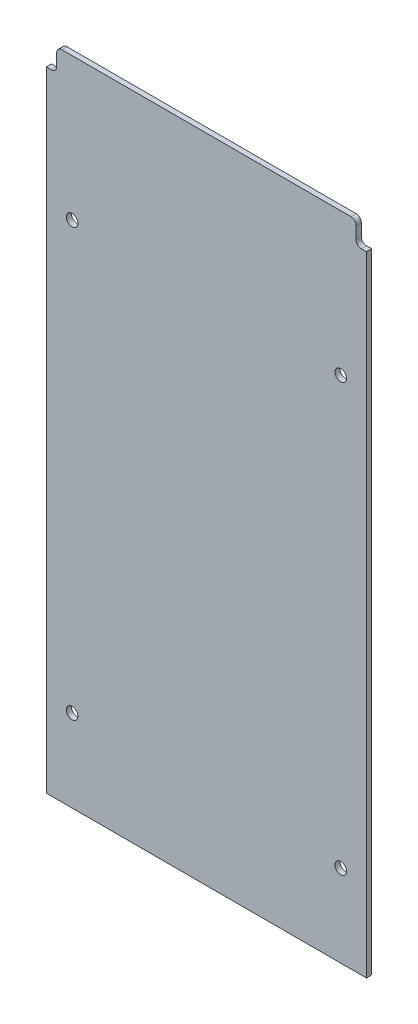
SolidWorks part; units mm, degrees
material "Acrylic (Medium-high impact)"
ref_plane "Front Plane" through (0, 0, 0) normal (0, 0, 1) x (1, 0, 0)
ref_plane "Top Plane" through (0, 0, 0) normal (0, 1, 0) x (1, 0, 0)
ref_plane "Right Plane" through (0, 0, 0) normal (1, 0, 0) x (0, 0, -1)
sketch "Sketch1" plane through (0, 0, 0) normal (0, 0, 1) x (1, 0, 0)
  line L0 (83.6105, -361.95) -> (83.6105, 175.26) construction
  line L1 (281.197, -361.95) -> (83.6105, -361.95)
  line L2 (281.197, -361.95) -> (281.197, 40.3225)
  line L3 (281.197, 40.3225) -> (83.6105, 40.3225)
  line L4 (83.6105, -361.95) -> (83.6105, 40.3225)
  line L5 (281.197, -361.95) -> (83.6105, 40.3225) construction
  line L6 (281.197, 40.3225) -> (83.6105, -361.95) construction
  line L7 (97.0763, 41.91) -> (153.4312, 41.91) construction
  point P4 (182.4037, -160.8138)
  dimension "D1" = 1.5875
extrude "Boss-Extrude1" add sketch "Sketch1" along normal blind 3.175
sketch "Sketch3" plane through (0, 0, 3.175) normal (0, 0, 1) x (1, 0, 0)
  line L0 (281.197, 40.3225) -> (83.6105, 40.3225) construction
  line L1 (89.9605, 40.3225) -> (83.6105, 40.3225)
  line L2 (89.9605, 40.3225) -> (89.9605, 26.3525)
  line L3 (89.9605, 26.3525) -> (83.6105, 26.3525)
  line L4 (83.6105, 40.3225) -> (83.6105, 26.3525)
  line L5 (89.9605, 40.3225) -> (83.6105, 26.3525) construction
  line L6 (89.9605, 26.3525) -> (83.6105, 40.3225) construction
  line L7 (83.6105, 40.3225) -> (83.6105, -361.95) construction
  line L8 (182.4037, 40.3225) -> (182.4037, -361.95) construction
  line L9 (83.6105, -361.95) -> (281.197, -361.95) construction
  line L10 (274.847, 26.3525) -> (281.197, 40.3225) construction
  line L11 (274.847, 40.3225) -> (281.197, 26.3525) construction
  line L12 (281.197, 40.3225) -> (281.197, 26.3525)
  line L13 (274.847, 26.3525) -> (281.197, 26.3525)
  line L14 (274.847, 40.3225) -> (274.847, 26.3525)
  line L15 (274.847, 40.3225) -> (281.197, 40.3225)
  point P4 (86.7855, 33.3375)
  point P17 (278.022, 33.3375)
  dimension "D1" = 13.97
  dimension "D2" = 6.35
extrude "Cut-Extrude1" cut sketch "Sketch3" against normal through all
fillet "Fillet1" radius 3.175 4 edges at (89.9605, 26.3525, 1.5875) (89.9605, 40.3225, 1.5875) (274.847, 40.3225, 1.5875) (274.847, 26.3525, 1.5875)
hole_wizard "1/4 Clearance Hole1" positions "Sketch4" profile "Sketch5" hole size "1/4" standard "ANSI Inch" end condition up to next
sketch "Sketch4" plane through (0, 0, 3.175) normal (0, 0, 1) x (1, 0, 0)
  point P0 (99.4854, -47.6219)
  point P3 (265.322, -47.625)
  point P6 (265.322, -311.15)
  point P9 (99.4855, -311.1469)
sketch "Sketch5" plane through (99.4854, -47.6219, 3.175) normal (1, 0, 0) x (0, -1, 0)
  line L0 (0, 0) -> (0, 3.175)
  line L1 (0, 3.175) -> (3.5712, 3.175)
  line L2 (3.5712, 3.175) -> (3.5712, 0)
  line L5 (3.5712, 0) -> (0, 0)
  line L11 (0, -6.35) -> (0, 107.95) construction
  dimension "Thru Hole Dia." = 7.1425
  dimension "Thru Hole Depth" = 3.175
